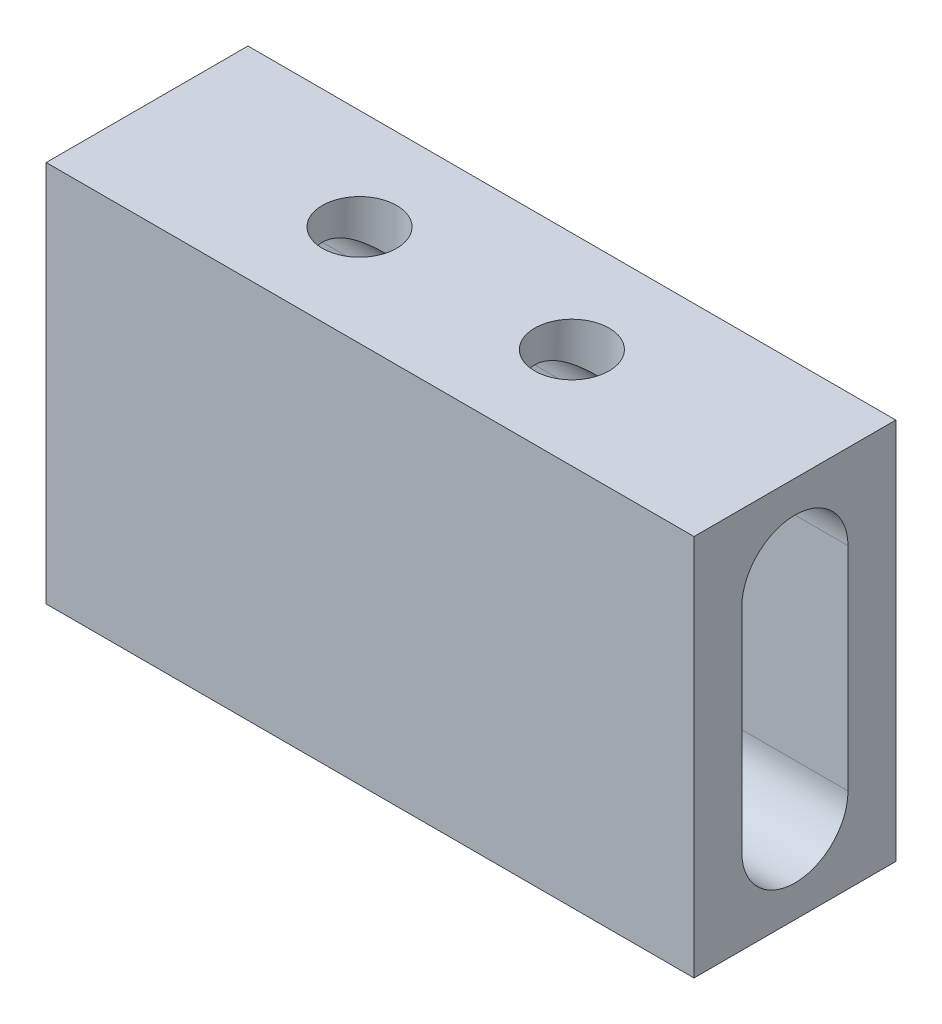
SolidWorks part; units mm, degrees
ref_plane "Front Plane" through (0, 0, 0) normal (0, 0, 1) x (1, 0, 0)
ref_plane "Top Plane" through (0, 0, 0) normal (0, 1, 0) x (1, 0, 0)
ref_plane "Right Plane" through (0, 0, 0) normal (1, 0, 0) x (0, 0, -1)
sketch "Sketch1" plane through (0, 0, 0) normal (1, 0, 0) x (0, 0, -1)
  line L0 (-10.2458, 11.3708) -> (-10.2458, 1.3708) construction
  line L1 (-14.9958, -2.6292) -> (-5.4958, -2.6292)
  line L2 (-14.9958, -2.6292) -> (-14.9958, 15.3708)
  line L3 (-14.9958, 15.3708) -> (-5.4958, 15.3708)
  line L4 (-5.4958, -2.6292) -> (-5.4958, 15.3708)
  line L5 (-7.7458, 11.3708) -> (-7.7458, 1.3708)
  line L6 (-12.7458, 11.3708) -> (-12.7458, 1.3708)
  arc A0 (-7.7458, 11.3708) -> (-12.7458, 11.3708) centre (-10.2458, 11.3708) ccw
  arc A1 (-12.7458, 1.3708) -> (-7.7458, 1.3708) centre (-10.2458, 1.3708) ccw
  point P6 (-10.2458, 6.3708)
  dimension "D4" = 2.5
  dimension "D1" = 18
  dimension "D2" = 9.5
  dimension "D3" = 4.75
  dimension "D5" = 10
  dimension "D6" = 4
extrude "Boss-Extrude1" add sketch "Sketch1" along normal blind 30.5
sketch "Sketch2" plane through (0, 15.3708, 0) normal (0, 1, 0) x (1, 0, 0)
  line L0 (30.5, -5.4958) -> (30.5, -14.9958) construction
  line L2 (30.5, -14.9958) -> (0, -14.9958) construction
  circle A0 centre (-10, -10.2458) radius 1.75
  circle A1 centre (-20, -10.2458) radius 1.75
  circle A2 centre (10, -10.2458) radius 1.75
  circle A3 centre (20, -10.2458) radius 1.75
  dimension "D1" = 3.5
  dimension "D2" = 10
  dimension "D3" = 10
  dimension "D4" = 20
  dimension "D5" = 10.5
  dimension "D6" = 4.75
  dimension "D7" = 4.75
  dimension "D8" = 4.75
  dimension "D9" = 4.75
extrude "Cut-Extrude1" cut sketch "Sketch2" against normal blind 5
